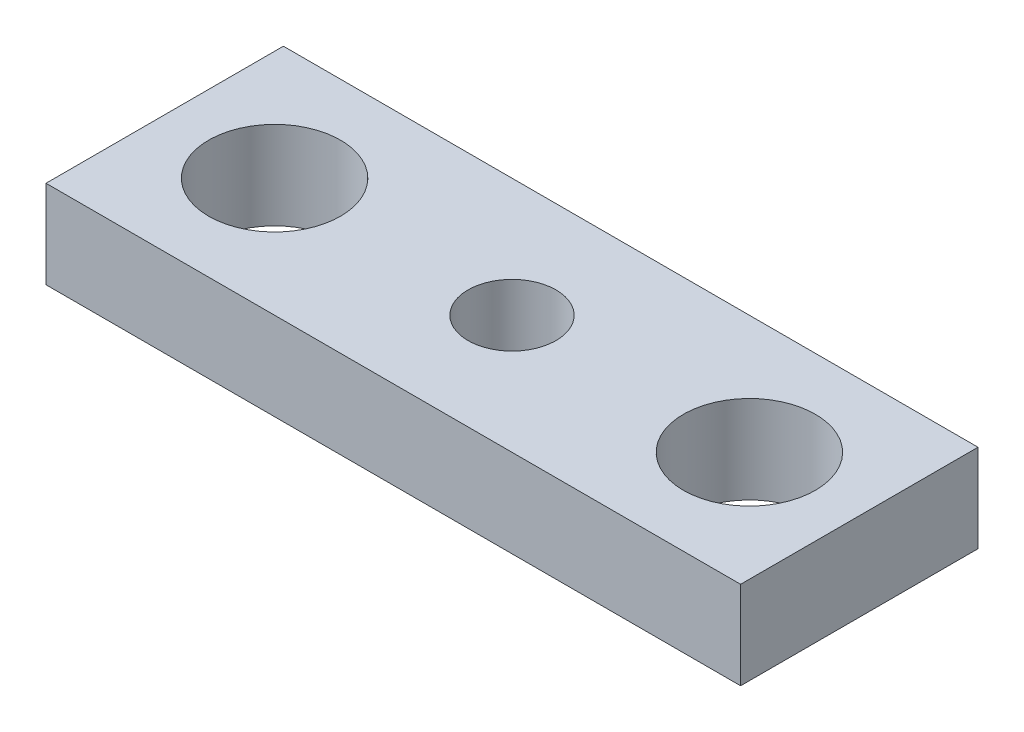
SolidWorks part; units mm, degrees
ref_plane "前视基准面" through (0, 0, 0) normal (0, 0, 1) x (1, 0, 0)
ref_plane "上视基准面" through (0, 0, 0) normal (0, 1, 0) x (1, 0, 0)
ref_plane "右视基准面" through (0, 0, 0) normal (1, 0, 0) x (0, 0, -1)
sketch "草图1" plane through (0, 0, 0) normal (0, 1, 0) x (1, 0, 0)
  line L1 (-39.5, 13.5) -> (39.5, 13.5)
  line L2 (-39.5, 13.5) -> (-39.5, -13.5)
  line L3 (-39.5, -13.5) -> (39.5, -13.5)
  line L4 (39.5, 13.5) -> (39.5, -13.5)
  line L5 (-39.5, 13.5) -> (39.5, -13.5) construction
  line L6 (-39.5, -13.5) -> (39.5, 13.5) construction
  point P0 (0, 0)
  dimension "D1" = 79
  dimension "D2" = 27
extrude "凸台-拉伸1" add sketch "草图1" along normal blind 10
sketch "草图2" plane through (0, 0, 0) normal (0, -1, 0) x (1, 0, 0)
  line L0 (-39.5, 0) -> (39.5, 0) construction
  line L1 (-39.5, -13.5) -> (-39.5, 13.5) construction
  line L2 (39.5, 13.5) -> (39.5, -13.5) construction
ref_plane "基准面1" through (0, 0, 0) normal (0, 0, 1) x (1, 0, 0)
sketch "草图3" plane through (0, 10, 0) normal (0, 1, 0) x (1, 0, 0)
  line L0 (-14.85, 0) -> (14.85, 0) construction
  line L1 (0, 13.5) -> (0, -13.5) construction
  line L2 (39.5, 13.5) -> (-39.5, 13.5) construction
  line L3 (-39.5, -13.5) -> (39.5, -13.5) construction
  circle A0 centre (-27, 0) radius 7.5
  circle A1 centre (27, 0) radius 7.5
  dimension "D1" = 15
  dimension "D2" = 54
extrude "切除-拉伸1" cut sketch "草图3" against normal through all contours A1 | A0
sketch "草图7" plane through (-39.5, 0, 0) normal (-1, 0, 0) x (0, 0, 1)
  line L0 (-13.5, 5) -> (13.5, 5) construction
  line L1 (-13.5, 10) -> (-13.5, 0) construction
  line L2 (13.5, 10) -> (13.5, 0) construction
ref_plane "基准面3" through (0, 5, 0) normal (0, 1, 0) x (1, 0, 0)
sketch "草图9" plane through (0, 5, 0) normal (0, 1, 0) x (1, 0, 0)
  line L0 (-44.1863, 9.5) -> (43.8901, 9.5) construction
  line L1 (39.5, 13.5) -> (-39.5, 13.5) construction
  line L2 (-39.5, -9.5) -> (39.6508, -9.5) construction
  line L3 (-39.5, 13.5) -> (-39.5, -13.5) construction
  line L4 (-39.5, -13.5) -> (39.5, -13.5) construction
  dimension "D1" = 4
  dimension "D2" = 4
sketch "草图10" plane through (0, 0, 0) normal (0, -1, 0) x (1, 0, 0)
  circle A0 centre (0, 0) radius 5
  dimension "D1" = 10
extrude "切除-拉伸2" cut sketch "草图10" against normal through all
